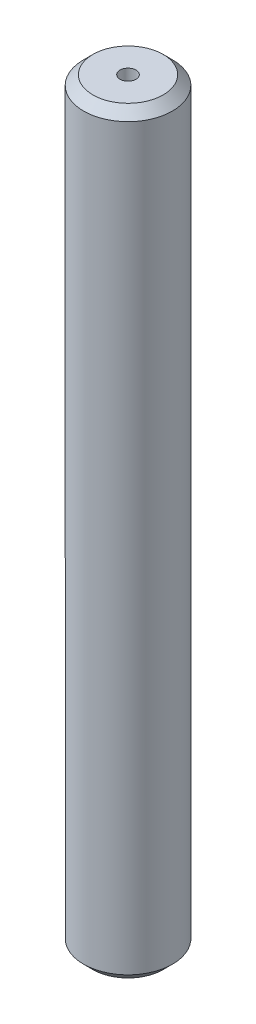
SolidWorks part; units mm, degrees
ref_plane "Front Plane" through (0, 0, 0) normal (0, 0, 1) x (1, 0, 0)
ref_plane "Top Plane" through (0, 0, 0) normal (0, 1, 0) x (1, 0, 0)
ref_plane "Right Plane" through (0, 0, 0) normal (1, 0, 0) x (0, 0, -1)
sketch "Sketch1" plane through (0, 0, 0) normal (0, 1, 0) x (1, 0, 0)
  circle A0 centre (0, 0) radius 5
  dimension "SHAFT_OD" = 10
extrude "Boss-Extrude1" add sketch "Sketch1" along normal blind 85.2304
sketch "Sketch2" plane through (0, 0, 0) normal (0, 1, 0) x (1, 0, 0)
  circle A0 centre (0, 0) radius 0.9002
  dimension "BORE_D" = 1.8003
extrude "Cut-Extrude1" cut sketch "Sketch2" along normal through all
chamfer "Chamfer1" distance 1.0479 angle 45 2 edges at (0, 85.2304, 5) (0, 0, 5)
